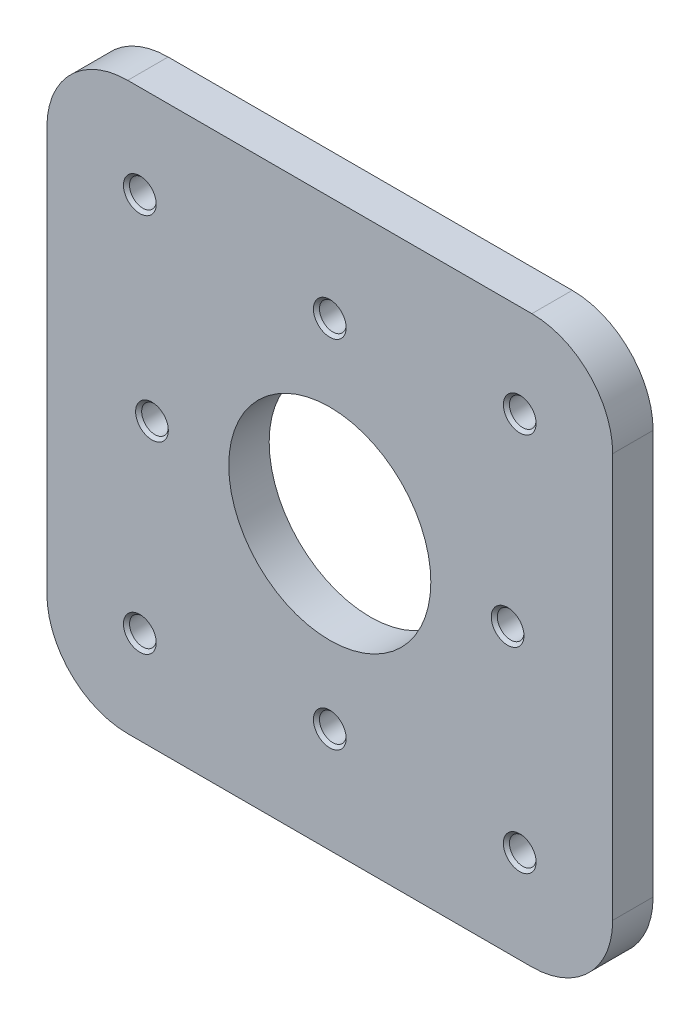
SolidWorks part; units mm, degrees
ref_plane "Front Plane" through (0, 0, 0) normal (0, 0, 1) x (1, 0, 0)
ref_plane "Top Plane" through (0, 0, 0) normal (0, 1, 0) x (1, 0, 0)
ref_plane "Right Plane" through (0, 0, 0) normal (1, 0, 0) x (0, 0, -1)
sketch "Sketch1" plane through (0, 0, 0) normal (0, 0, 1) x (1, 0, 0)
  line L0 (0, 0) -> (0, 22) construction
  line L1 (-35, -35) -> (35, -35)
  line L2 (-35, -35) -> (-35, 35)
  line L3 (-35, 35) -> (35, 35)
  line L4 (35, -35) -> (35, 35)
  line L5 (-35, -35) -> (35, 35) construction
  line L6 (-35, 35) -> (35, -35) construction
  line L7 (-23.5, -23.5) -> (23.5, -23.5) construction
  line L8 (-23.5, -23.5) -> (-23.5, 23.5) construction
  line L9 (-23.5, 23.5) -> (23.5, 23.5) construction
  line L10 (23.5, -23.5) -> (23.5, 23.5) construction
  line L11 (-23.5, -23.5) -> (23.5, 23.5) construction
  line L12 (-23.5, 23.5) -> (23.5, -23.5) construction
  circle A0 centre (0, 0) radius 12.5
  circle A1 centre (0, 0) radius 22 construction
  circle A2 centre (-23.5, 23.5) radius 2.5 construction
  circle A3 centre (23.5, 23.5) radius 2.5 construction
  circle A4 centre (23.5, -23.5) radius 2.5 construction
  circle A5 centre (-23.5, -23.5) radius 2.5 construction
  circle A6 centre (0, 22) radius 2.5 construction
  circle A7 centre (22, 0) radius 2.5 construction
  circle A8 centre (0, -22) radius 2.5 construction
  circle A9 centre (-22, 0) radius 2.5 construction
  point P0 (0, 0)
  point P28 (0, 0)
  dimension "D2" = 25
  dimension "D4" = 44
  dimension "D5" = 5
  dimension "D6" = 5
  dimension "D1" = 70
  dimension "D3" = 47
  dimension "D7" = 4
base flange "Base-Flange1" sketch "Sketch1" thickness 5 reverse thickness direction no parameters "D1"=2
hole_wizard "M4x0.7 Tapped Hole1" positions "Sketch6" profile "Sketch7" tap size "M4x0.7" standard "ANSI Metric"
sketch "Sketch6" plane through (0, 0, 0) normal (0, 0, 1) x (1, 0, 0)
  point P0 (0, 22)
  point P3 (-22, 0)
  point P6 (0, -22)
  point P9 (22, 0)
sketch "Sketch7" plane through (0, 22, 0) normal (1, 0, 0) x (0, -1, 0)
  line L0 (0, 0) -> (0, 11.0914)
  line L1 (0, 11.0914) -> (1.65, 10.1)
  line L2 (1.65, 10.1) -> (1.65, 0.375)
  line L3 (1.65, 0.375) -> (2.025, 0)
  line L5 (2.025, 0) -> (0, 0)
  line L6 (-1.65, 0.375) -> (-2.025, 0) construction
  line L10 (0, 11.0914) -> (-1.65, 10.1) construction
  line L11 (0, -6.35) -> (0, 107.95) construction
  dimension "Tap Drill Dia." = 3.3
  dimension "Tap Drill Depth" = 10.1
  dimension "Near C'Sink Dia." = 4.05
  dimension "Near C'Sink Angle" = 90
  dimension "Drill Angle" = 118
hole_wizard "M4x0.7 Tapped Hole2" positions "Sketch8" profile "Sketch9" tap size "M4x0.7" standard "ANSI Metric"
sketch "Sketch8" plane through (0, 0, 0) normal (0, 0, 1) x (1, 0, 0)
  point P0 (-23.5, 23.5)
  point P3 (23.5, 23.5)
  point P6 (23.5, -23.5)
  point P9 (-23.5, -23.5)
sketch "Sketch9" plane through (-23.5, 23.5, 0) normal (1, 0, 0) x (0, -1, 0)
  line L0 (0, 0) -> (0, 11.0914)
  line L1 (0, 11.0914) -> (1.65, 10.1)
  line L2 (1.65, 10.1) -> (1.65, 0.375)
  line L3 (1.65, 0.375) -> (2.025, 0)
  line L5 (2.025, 0) -> (0, 0)
  line L6 (-1.65, 0.375) -> (-2.025, 0) construction
  line L10 (0, 11.0914) -> (-1.65, 10.1) construction
  line L11 (0, -6.35) -> (0, 107.95) construction
  dimension "Tap Drill Dia." = 3.3
  dimension "Tap Drill Depth" = 10.1
  dimension "Near C'Sink Dia." = 4.05
  dimension "Near C'Sink Angle" = 90
  dimension "Drill Angle" = 118
fillet "Fillet1" radius 10 4 edges at (35, 35, -2.5) (35, -35, -2.5) (-35, -35, -2.5) (-35, 35, -2.5)
sketch "Bend-Lines1" [suppressed] plane through (0, 0, 0) normal (0, 1, 0) x (1, 0, 0)
sketch "Bounding-Box1" [suppressed] plane through (0, 0, 0) normal (0, 1, 0) x (1, 0, 0)
sheet metal parameters "Sheet-Metal1" thickness 5 parameters "D1"=2
flat pattern "Flat-Pattern1" [suppressed]
sketch "Bend-Lines2" plane through (0, 0, 0) normal (0, 1, 0) x (1, 0, 0)
sketch3d "Bounding-Box2" [suppressed]
  line L0 (35, -35, 0) -> (-35, -35, 0) construction
  line L1 (35, 35, 0) -> (-35, 35, 0) construction
  line L2 (35, -35, 0) -> (35, 35, 0) construction
  line L3 (-35, -35, 0) -> (-35, 35, 0) construction
sheet metal parameters "Sheet-Metal2" thickness 5 parameters "D1"=2
flat pattern "Flat-Pattern1"
sketch "Bend-Lines2" plane through (0, 0, 0) normal (0, 1, 0) x (1, 0, 0)
sketch3d "Bounding-Box2" [suppressed]
  line L0 (-35, -35, 0) -> (35, -35, 0) construction
  line L1 (-35, 35, 0) -> (35, 35, 0) construction
  line L2 (-35, -35, 0) -> (-35, 35, 0) construction
  line L3 (35, -35, 0) -> (35, 35, 0) construction
sheet metal parameters "Sheet-Metal3" thickness 5 parameters "D1"=2
flat pattern "Flat-Pattern1"
sketch "Bend-Lines2" plane through (0, 0, 0) normal (0, 1, 0) x (1, 0, 0)
sketch3d "Bounding-Box2" [suppressed]
  line L0 (-35, -35, 0) -> (35, -35, 0) construction
  line L1 (-35, 35, 0) -> (35, 35, 0) construction
  line L2 (-35, -35, 0) -> (-35, 35, 0) construction
  line L3 (35, -35, 0) -> (35, 35, 0) construction
